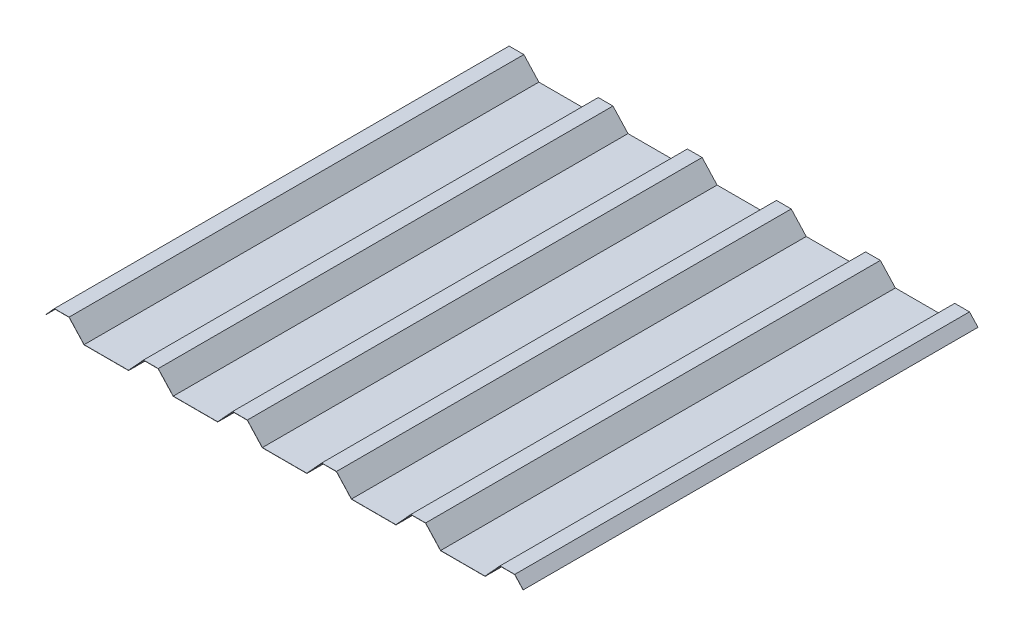
SolidWorks part; units mm, degrees
ref_plane "Plano frontal" through (0, 0, 0) normal (0, 0, 1) x (1, 0, 0)
ref_plane "Plano superior" through (0, 0, 0) normal (0, 1, 0) x (1, 0, 0)
ref_plane "Plano direito" through (0, 0, 0) normal (1, 0, 0) x (0, 0, -1)
sketch "Esboço1" plane through (0, 0, 0) normal (0, 0, 1) x (1, 0, 0)
  line L0 (0, 0) -> (32, 0)
  line L1 (65, -36) -> (163, -36)
  line L3 (0, 0) -> (-33, -36)
  line L4 (32, 0) -> (65, -36)
  line L5 (196, 0) -> (228, 0)
  line L6 (261, -36) -> (359, -36)
  line L7 (196, 0) -> (163, -36)
  line L8 (228, 0) -> (261, -36)
  line L9 (-33, -36) -> (-131, -36)
  line L10 (392, 0) -> (424, 0)
  line L11 (457, -36) -> (555, -36)
  line L12 (392, 0) -> (359, -36)
  line L13 (424, 0) -> (457, -36)
  line L14 (588, 0) -> (620, 0)
  line L15 (653, -36) -> (751, -36)
  line L16 (588, 0) -> (555, -36)
  line L17 (620, 0) -> (653, -36)
  line L18 (-196, 0) -> (-164, 0)
  line L19 (-196, 0) -> (-214.2729, -20)
  line L20 (-164, 0) -> (-131, -36)
  line L23 (784, 0) -> (816, 0)
  line L24 (784, 0) -> (751, -36)
  line L25 (816, 0) -> (834.5668, -20)
  point P8 (16, -36)
  point P12 (212, -36)
  point P18 (408, -36)
  point P23 (604, -36)
  point P25 (834.248, -21.2165)
  dimension "D1" = 98
  dimension "D2" = 98
extrude "Extrusão-Fina1" add sketch "Esboço1" along normal blind 1000 thin contours L19 L18 L20 L9 L3 L0 L4 L1 L7 L5 L8 L6 L12 L10 L13 L11 L16 L14 L17 L15 L24 L23 L25 thin type one direction wall 0.5
